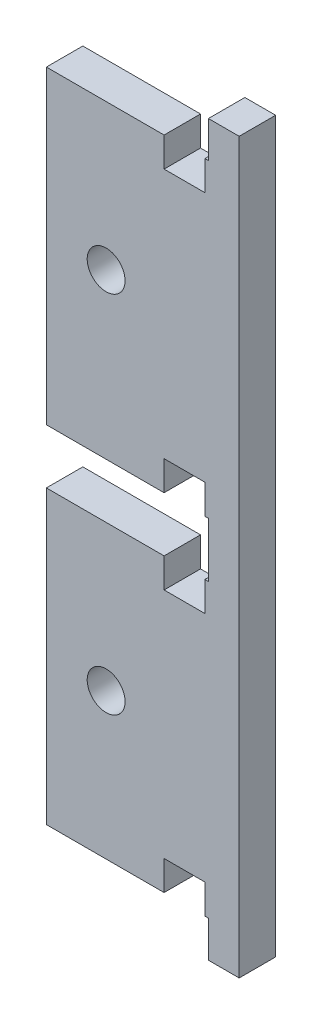
SolidWorks part; units mm, degrees
material "AISI 4130 Steel, annealed at 865C"
ref_plane "X-Y Datum" through (0, 0, 0) normal (0, 0, 1) x (1, 0, 0)
ref_plane "X-Z Datum" through (0, 0, 0) normal (0, 1, 0) x (1, 0, 0)
ref_plane "Y-Z Datum" through (0, 0, 0) normal (1, 0, 0) x (0, 0, -1)
sketch "Sketch2" plane through (0, 0, 0) normal (0, 0, 1) x (1, 0, 0)
  line L0 (32.9006, 127) -> (0, 127) construction
  line L1 (0, 0) -> (40.64, 0)
  line L2 (0, 0) -> (0, 127)
  line L3 (0, 127) -> (40.64, 127)
  line L4 (40.64, 0) -> (40.64, 127)
  point P7 (17.4625, 31.75)
  point P8 (17.4625, 95.25)
  dimension "D1" = 40.64
extrude "Boss-Extrude1" add sketch "Sketch2" along normal blind 6.35
hole_wizard "M6 Clearance Hole1" positions "Sketch3" profile "Sketch4" hole size "M6" standard "ANSI Metric" end condition through all
sketch "Sketch3" plane through (0, 0, 6.35) normal (0, 0, 1) x (1, 0, 0)
  point P0 (17.4625, 31.75)
  point P3 (17.4625, 95.25)
sketch "Sketch4" plane through (17.4625, 31.75, 6.35) normal (1, 0, 0) x (0, -1, 0)
  line L0 (0, 0) -> (0, 6.35)
  line L1 (0, 6.35) -> (3.3, 6.35)
  line L2 (3.3, 6.35) -> (3.3, 0)
  line L5 (3.3, 0) -> (0, 0)
  line L11 (0, -6.35) -> (0, 107.95) construction
  dimension "Thru Hole Dia." = 6.6
  dimension "Thru Hole Depth" = 6.35
sketch "Sketch5" plane through (0, 0, 6.35) normal (0, 0, 1) x (1, 0, 0)
  line L0 (7.0505, 127) -> (7.0505, 0)
  line L1 (40.64, 127) -> (0, 127) construction
  line L2 (0, 0) -> (40.64, 0) construction
  circle A0 centre (17.4625, 95.25) radius 3.3 construction
  point P6 (14.1625, 95.25)
  line M4 (0, 127) -> (0, 0)
  line M5 (0, 0) -> (40.64, 0)
  line M7 (40.64, 127) -> (0, 127)
  dimension "D1" = 7.112
extrude "Cut-Extrude1" cut sketch "Sketch5" against normal through all and the other way through all contours L0 M7 M4 M5 region at (3.5253, 63.5, 6.35)
sketch "Sketch6" plane through (0, 0, 6.35) normal (0, 0, 1) x (1, 0, 0)
  line L0 (-3.175, 120.65) -> (36.0756, 120.65)
  line L1 (36.0756, 120.65) -> (36.0756, 130.175)
  line L2 (36.0756, 130.175) -> (-3.175, 130.175)
  line L3 (-3.175, 130.175) -> (-3.175, 120.65)
  line L4 (0, 123.825) -> (32.9006, 123.825)
  line L5 (32.9006, 123.825) -> (32.9006, 127)
  line L6 (32.9006, 127) -> (0, 127)
  line L7 (0, 127) -> (0, 123.825)
  line L8 (0, 123.825) -> (32.9006, 123.825)
  line L9 (32.9006, 123.825) -> (32.9006, 127)
  line L10 (32.9006, 127) -> (0, 127)
  line L11 (0, 127) -> (0, 123.825)
  line L12 (0, 60.325) -> (32.9006, 60.325)
  line L13 (32.9006, 60.325) -> (32.9006, 63.5)
  line L14 (32.9006, 63.5) -> (0, 63.5)
  line L15 (0, 63.5) -> (0, 60.325)
  line L16 (0, 60.325) -> (32.9006, 60.325)
  line L17 (32.9006, 60.325) -> (32.9006, 63.5)
  line L18 (32.9006, 63.5) -> (0, 63.5)
  line L19 (0, 63.5) -> (0, 60.325)
  line L24 (0, 0) -> (34.925, 0)
  line L25 (34.925, 0) -> (34.925, 3.175)
  line L26 (34.925, 3.175) -> (0, 3.175)
  line L27 (0, 3.175) -> (0, 0)
  line L28 (36.0756, 66.675) -> (-3.175, 66.675)
  line L29 (-3.175, 66.675) -> (-3.175, 57.15)
  line L30 (-3.175, 57.15) -> (36.0756, 57.15)
  line L31 (36.0756, 57.15) -> (36.0756, 66.675)
  line L32 (38.1, 6.35) -> (-3.175, 6.35)
  line L33 (-3.175, 6.35) -> (-3.175, -3.175)
  line L34 (-3.175, -3.175) -> (38.1, -3.175)
  line L35 (38.1, -3.175) -> (38.1, 6.35)
  line L36 (35.2819, 127) -> (35.2819, 0)
  line L37 (40.64, 127) -> (7.0505, 127) construction
  line L38 (7.0505, 0) -> (40.64, 0) construction
  line M19 (7.0505, 127) -> (7.0505, 0)
  line M20 (7.0505, 0) -> (40.64, 0)
  line M22 (40.64, 127) -> (7.0505, 127)
  dimension "D5" = 2.3813
  dimension "D1" = 0
  dimension "D2" = 0
  dimension "D4" = 3.175
extrude "Cut-Extrude2" cut sketch "Sketch6" against normal through all contours L36 L9 L8 L0 M22 M19 | L8 L9 M22 M19 | L36 L28 L18 L17 L16 L30 M19 | L17 L18 L16 M19 | L36 L32 L26 L25 M19 M20 | L25 L26 M19 M20 region at (22.1716, 122.4845, 6.35) region at (19.9756, 125.4125, 6.35) region at (21.1662, 66.3771, 6.35) region at (19.9756, 61.9125, 6.35) region at (21.3402, 4.7229, 6.35) region at (20.9878, 1.5875, 6.35)
sketch "Sketch7" plane through (0, 0, 6.35) normal (0, 0, 1) x (1, 0, 0)
  line L0 (34.671, 115.5065) -> (27.559, 115.5065)
  line L5 (27.559, 121.031) -> (27.559, 115.5065)
  line L18 (34.29, 120.65) -> (27.94, 120.65)
  line L19 (34.29, 120.65) -> (34.29, 115.8875)
  line L20 (34.29, 115.8875) -> (27.94, 115.8875)
  line L21 (27.94, 120.65) -> (27.94, 115.8875)
  line L22 (34.29, 71.4375) -> (27.94, 71.4375)
  line L23 (34.29, 71.4375) -> (34.29, 66.675)
  line L24 (34.29, 66.675) -> (27.94, 66.675)
  line L25 (27.94, 71.4375) -> (27.94, 66.675)
  line L26 (34.29, 57.15) -> (27.94, 57.15)
  line L27 (34.29, 57.15) -> (34.29, 52.3875)
  line L28 (34.29, 52.3875) -> (27.94, 52.3875)
  line L29 (27.94, 57.15) -> (27.94, 52.3875)
  line L30 (34.29, 11.1125) -> (27.94, 11.1125)
  line L31 (34.29, 11.1125) -> (34.29, 6.35)
  line L32 (34.29, 6.35) -> (27.94, 6.35)
  line L33 (27.94, 11.1125) -> (27.94, 6.35)
  line L34 (34.671, 121.031) -> (27.559, 121.031)
  line L35 (34.671, 121.031) -> (34.671, 115.5065)
  line L36 (34.671, 66.294) -> (27.559, 66.294)
  line L37 (27.559, 71.8185) -> (27.559, 66.294)
  line L38 (34.671, 71.8185) -> (27.559, 71.8185)
  line L39 (34.671, 71.8185) -> (34.671, 66.294)
  line L40 (34.671, 52.0065) -> (27.559, 52.0065)
  line L41 (27.559, 57.531) -> (27.559, 52.0065)
  line L42 (34.671, 57.531) -> (27.559, 57.531)
  line L43 (34.671, 57.531) -> (34.671, 52.0065)
  line L44 (34.671, 5.969) -> (27.559, 5.969)
  line L45 (27.559, 11.4935) -> (27.559, 5.969)
  line L46 (34.671, 11.4935) -> (27.559, 11.4935)
  line L47 (34.671, 11.4935) -> (34.671, 5.969)
  line M4 (35.2819, 120.65) -> (7.0505, 120.65)
  line M6 (7.0505, 66.675) -> (35.2819, 66.675)
  line M8 (35.2819, 57.15) -> (7.0505, 57.15)
  line M10 (7.0505, 6.35) -> (35.2819, 6.35)
  dimension "D1" = 0.381
extrude "Cut-Extrude3" cut sketch "Sketch7" against normal through all contours L30 L33 L31 M10 | L47 L46 L45 L33 L30 L31 M10 | L47 L45 L44 M10 | L29 L28 L27 M8 | L43 L27 L28 L29 L41 L40 M8 | L43 L42 L41 M8 | L39 L37 L36 M6 | L22 L25 L23 M6 | L39 L38 L37 L25 L22 L23 M6 | L21 L20 L19 M4 | L35 L19 L20 L21 L5 L0 M4 | L35 L34 L5 M4 region at (31.115, 115.5943, 6.35) region at (31.115, 120.8405, 6.35) region at (31.115, 118.2688, 6.35) region at (31.115, 69.0563, 6.35) region at (31.115, 71.5253, 6.35) region at (31.115, 66.4845, 6.35) region at (31.115, 54.7688, 6.35) region at (34.4805, 57.0622, 6.35) region at (31.115, 57.3405, 6.35) region at (31.115, 8.7312, 6.35) region at (31.115, 11.2003, 6.35) region at (31.115, 6.1595, 6.35)
